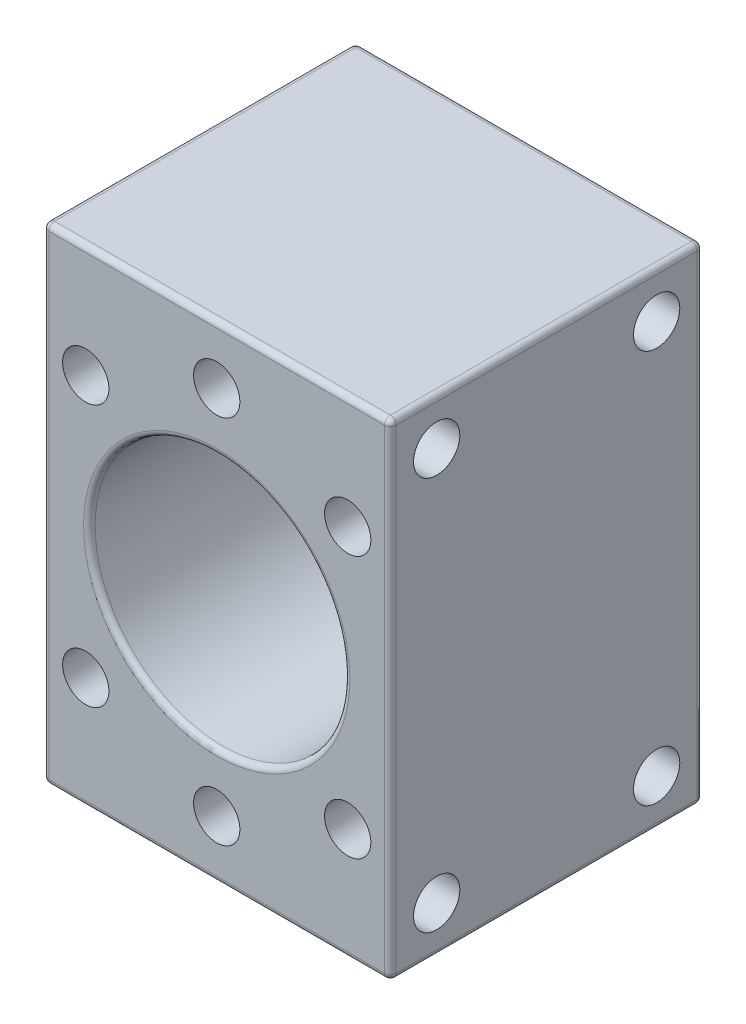
SolidWorks part; units mm, degrees
ref_plane "Front Plane" through (0, 0, 0) normal (0, 0, 1) x (1, 0, 0)
ref_plane "Top Plane" through (0, 0, 0) normal (0, 1, 0) x (1, 0, 0)
ref_plane "Right Plane" through (0, 0, 0) normal (1, 0, 0) x (0, 0, -1)
sketch "Sketch1" plane through (0, 0, 0) normal (0, 0, 1) x (1, 0, 0)
  line L3 (-15, -21) -> (15, -21)
  line L4 (-15, -21) -> (-15, 21)
  line L5 (-15, 21) -> (15, 21)
  line L6 (15, -21) -> (15, 21)
  line L7 (-15, -21) -> (15, 21) construction
  line L8 (-15, 21) -> (15, -21) construction
  dimension "D4" = 30
  dimension "D5" = 42
extrude "Boss-Extrude1" add sketch "Sketch1" along normal mid plane 27
sketch "Sketch2" plane through (0, 0, 13.5) normal (0, 0, 1) x (1, 0, 0)
  circle A0 centre (0, 0) radius 11
  dimension "D1" = 22
extrude "Cut-Extrude1" cut sketch "Sketch2" against normal through all
sketch "Sketch3" plane through (0, 0, 13.5) normal (0, 0, 1) x (1, 0, 0)
  line L0 (0, 21) -> (0, -21) construction
  line L1 (0, 0) -> (-19.8057, 19.8057) construction
  line L2 (0, 0) -> (19.0248, 19.0248) construction
  circle A2 centre (0, 0) radius 16 construction
  circle A3 centre (-11.3137, 11.3137) radius 2
  circle A4 centre (0, 16) radius 2
  circle A5 centre (11.3137, 11.3137) radius 2
  circle A6 centre (11.3137, -11.3137) radius 2
  circle A7 centre (0, -16) radius 2
  circle A8 centre (-11.3137, -11.3137) radius 2
  dimension "D3" = 32
  dimension "D4" = 4
  dimension "D5" = 4
  dimension "D6" = 4
  dimension "D7" = 4
  dimension "D8" = 4
  dimension "D9" = 4
  dimension "D1" = 45
  dimension "D2" = 45
extrude "Cut-Extrude2" cut sketch "Sketch3" against normal blind 8
sketch "Sketch6" plane through (15, 0, 0) normal (1, 0, 0) x (0, 0, -1)
  line L1 (-9.5, -17) -> (9.5, -17) construction
  line L2 (-9.5, -17) -> (-9.5, 17) construction
  line L3 (-9.5, 17) -> (9.5, 17) construction
  line L4 (9.5, -17) -> (9.5, 17) construction
  line L5 (-9.5, -17) -> (9.5, 17) construction
  line L6 (-9.5, 17) -> (9.5, -17) construction
  circle A0 centre (9.5, 17) radius 2
  circle A1 centre (-9.5, 17) radius 2
  circle A2 centre (9.5, -17) radius 2
  circle A3 centre (-9.5, -17) radius 2
  point P12 (0, 0)
  dimension "D1" = 4
  dimension "D2" = 4
  dimension "D3" = 4
  dimension "D4" = 4
  dimension "D5" = 34
  dimension "D6" = 19
extrude "Cut-Extrude3" cut sketch "Sketch6" against normal blind 8
fillet "Fillet1" radius 0.5 14 edges at (0, -21, -13.5) (-15, -21, 0) (15, 0, -13.5) (15, -21, 0) (0, -21, 13.5) (-15, 0, 13.5) (11, 0, 13.5) (15, 0, 13.5) (-15, 21, 0) (0, 21, -13.5) (15, 21, 0) (0, 21, 13.5) (11, 0, -13.5) (-15, 0, -13.5)
equation "\"D6@Sketch3\"=\"D5@Sketch3\""
equation "\"D9@Sketch3\"=\"D5@Sketch3\""
equation "\"D8@Sketch3\"=\"D5@Sketch3\""
equation "\"D7@Sketch3\"=\"D5@Sketch3\""
equation "\"D4@Sketch3\"=\"D5@Sketch3\""
equation "\"D1@Sketch6\"=\"D2@Sketch6\""
equation "\"D4@Sketch6\"=\"D2@Sketch6\""
equation "\"D3@Sketch6\"=\"D2@Sketch6\""
